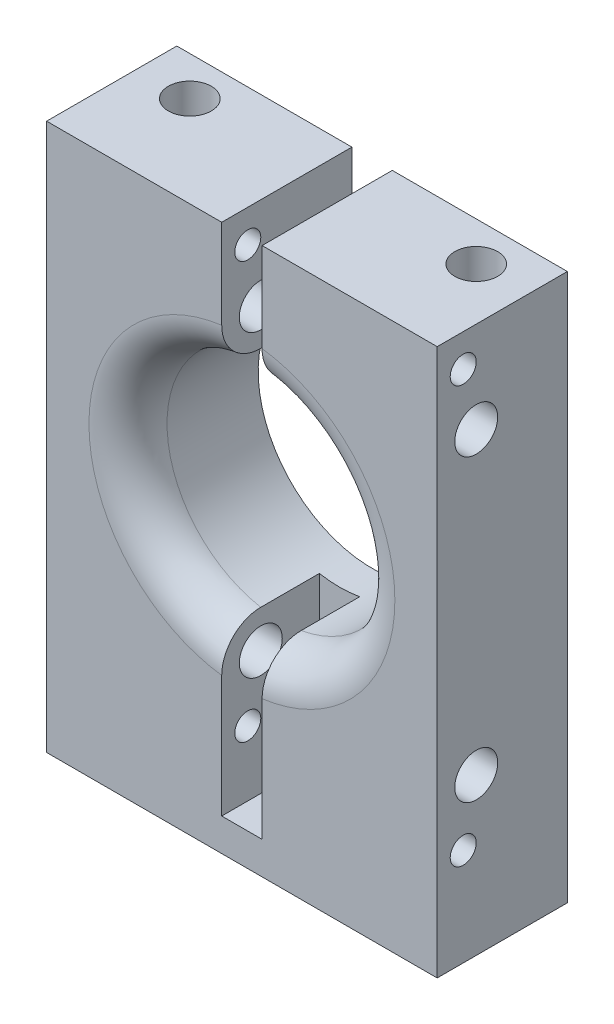
SolidWorks part; units mm, degrees
material "6061 合金"
ref_plane "前视基准面" through (0, 0, 0) normal (0, 0, 1) x (1, 0, 0)
ref_plane "上视基准面" through (0, 0, 0) normal (0, 1, 0) x (1, 0, 0)
ref_plane "右视基准面" through (0, 0, 0) normal (1, 0, 0) x (0, 0, -1)
other "Configuration Table"
sketch "草图1" plane through (0, 0, 0) normal (0, 0, 1) x (1, 0, 0)
  line L1 (-15, 18.5) -> (15, 18.5)
  line L2 (-15, 18.5) -> (-15, -23.5)
  line L3 (-15, -23.5) -> (15, -23.5)
  line L4 (15, 18.5) -> (15, -23.5)
  circle A0 centre (0, 0) radius 8.75
  point P7 (0, 18.5)
  dimension "D1" = 17.5
  dimension "D2" = 42
  dimension "D3" = 30
  dimension "D4" = 23.5
extrude "凸台-拉伸1" add sketch "草图1" along normal blind 10
sketch "草图3" plane through (15, 0, 0) normal (1, 0, 0) x (0, 0, -1)
  line L0 (-8, 16) -> (-8, -16) construction
  line L1 (-10, -23.5) -> (-10, 18.5) construction
  circle A0 centre (-8, -16) radius 1
  circle A1 centre (-8, 16) radius 1
  point P4 (-8, 0)
  dimension "D2" = 2
  dimension "D1" = 32
  dimension "D3" = 2
extrude "切除-拉伸1" cut sketch "草图3" against normal through all and the other way through all
hole_wizard "M4 螺纹孔1" positions "草图6" profile "草图5" tap size "M4" standard "GB" end condition through all
sketch "草图6" plane through (0, 18.5, 0) normal (0, 1, 0) x (1, 0, 0)
  line L0 (-11, -3) -> (11, -3) construction
  line L2 (15, 0) -> (-15, 0) construction
  point P0 (-11, -3)
  point P2 (11, -3)
  point P7 (0, -3)
  dimension "D1" = 3
  dimension "D2" = 22
sketch "草图5" plane through (-11, 18.5, 3) normal (1, 0, 0) x (0, 0, 1)
  line L0 (0, 0) -> (0, 42)
  line L1 (0, 42) -> (1.65, 42)
  line L2 (1.65, 42) -> (1.65, 0)
  line L5 (1.65, 0) -> (0, 0)
  line L11 (0, -6.35) -> (0, 107.95) construction
  dimension "通孔螺纹孔钻头直径" = 3.3
  dimension "通孔螺纹孔钻头深度" = 42
cosmetic thread "孔螺蚊线1" parameters "D2"=4
cosmetic thread "孔螺蚊线2" parameters "D2"=4
sketch "草图9" plane through (0, 0, 0) normal (1, 0, 0) x (0, 0, -1)
  line L0 (-10, -23.5) -> (-10, 18.5) construction
  circle A0 centre (-19, 0) radius 9 construction
  dimension "D1" = 18
hole_wizard "M4 螺纹孔2" positions "草图10" profile "草图11" tap size "M4" standard "GB" end condition through all
sketch "草图10" plane through (15, 0, 0) normal (1, 0, 0) x (0, 0, -1)
  line L0 (-7, 11.5) -> (-7, -11.5) construction
  line L2 (-10, -23.5) -> (-10, 18.5) construction
  point P0 (-7, -11.5)
  point P2 (-7, 11.5)
  point P8 (-7, 0)
  dimension "D1" = 23
  dimension "D2" = 3
sketch "草图11" plane through (15, -11.5, 7) normal (0, 1, 0) x (0, 0, -1)
  line L0 (0, 0) -> (0, 30)
  line L1 (0, 30) -> (1.65, 30)
  line L2 (1.65, 30) -> (1.65, 0)
  line L5 (1.65, 0) -> (0, 0)
  line L11 (0, -6.35) -> (0, 107.95) construction
  dimension "通孔螺纹孔钻头直径" = 3.3
  dimension "通孔螺纹孔钻头深度" = 30
cosmetic thread "孔螺蚊线3" parameters "D2"=4
cosmetic thread "孔螺蚊线4" parameters "D2"=4
fillet "圆角1" radius 3 1 edges at (8.75, 0, 10)
sketch "草图12" plane through (0, 0, 10) normal (0, 0, 1) x (1, 0, 0)
  line L0 (15, 18.5) -> (-15, 18.5) construction
  line L1 (-1.55, 18.5) -> (1.55, 18.5)
  line L2 (-1.55, 18.5) -> (-1.55, -21)
  line L3 (-1.55, -21) -> (1.55, -21)
  line L4 (1.55, 18.5) -> (1.55, -21)
  line L6 (-15, -23.5) -> (15, -23.5) construction
  point P8 (0, -21)
  point P10 (0, -23.5)
  dimension "D1" = 3.1
  dimension "D2" = 2.5
extrude "切除-拉伸3" cut sketch "草图12" against normal blind 7.5
sketch "草图13" plane through (0, 0, 2.5) normal (0, 0, 1) x (1, 0, 0)
  line L3 (1.55, 8.6116) -> (1.55, 18.5)
  line L4 (1.55, 18.5) -> (-1.55, 18.5)
  line L5 (-1.55, 18.5) -> (-1.55, 8.6116)
  line L6 (1.55, 8.6116) -> (1.55, 18.5)
  line L7 (1.55, 18.5) -> (-1.55, 18.5)
  line L8 (-1.55, 18.5) -> (-1.55, 8.6116)
  arc A1 (1.55, 8.6116) -> (-1.55, 8.6116) centre (0, 0) ccw
  arc A2 (1.55, 8.6116) -> (-1.55, 8.6116) centre (0, 0) ccw
  dimension "D1" = 0
extrude "切除-拉伸4" cut sketch "草图13" against normal blind 6
